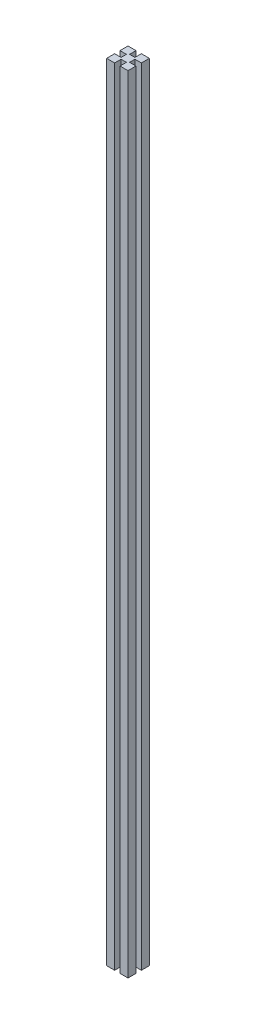
SolidWorks part; units mm, degrees
ref_plane "Front Plane" through (0, 0, 0) normal (0, 0, 1) x (1, 0, 0)
ref_plane "Top Plane" through (0, 0, 0) normal (0, 1, 0) x (1, 0, 0)
ref_plane "Right Plane" through (0, 0, 0) normal (1, 0, 0) x (0, 0, -1)
sketch "Sketch1" plane through (0, 0, 0) normal (0, 1, 0) x (1, 0, 0)
  line L1 (-10, -10) -> (10, -10)
  line L2 (-10, -10) -> (-10, 10)
  line L3 (-10, 10) -> (10, 10)
  line L4 (10, -10) -> (10, 10)
  line L5 (-10, -10) -> (10, 10) construction
  line L6 (-10, 10) -> (10, -10) construction
  point P0 (0, 0)
  dimension "D1" = 20
  dimension "D2" = 20
extrude "Boss-Extrude1" add sketch "Sketch1" along normal blind 368.3 and the other way blind 368.3
sketch "Sketch2" plane through (0, 0, 0) normal (0, 1, 0) x (1, 0, 0)
  line L0 (-2.5, 4) -> (2.5, 4)
  line L1 (-2.5, 4) -> (-2.5, 16)
  line L2 (-2.5, 16) -> (2.5, 16)
  line L3 (2.5, 4) -> (2.5, 16)
  line L4 (-2.5, 4) -> (2.5, 16) construction
  line L5 (-2.5, 16) -> (2.5, 4) construction
  line L6 (4, 2.5) -> (16, 2.5)
  line L7 (4, 2.5) -> (4, -2.5)
  line L8 (4, -2.5) -> (16, -2.5)
  line L9 (16, 2.5) -> (16, -2.5)
  line L10 (4, 2.5) -> (16, -2.5) construction
  line L11 (4, -2.5) -> (16, 2.5) construction
  line L12 (-10, 10) -> (10, -10) construction
  line L13 (-16, 2.5) -> (-4, -2.5) construction
  line L14 (-4, 2.5) -> (-16, -2.5) construction
  line L15 (-4, -2.5) -> (-16, -2.5)
  line L16 (-16, 2.5) -> (-16, -2.5)
  line L17 (-4, 2.5) -> (-16, 2.5)
  line L18 (-4, 2.5) -> (-4, -2.5)
  line L19 (2.5, -4) -> (2.5, -16)
  line L20 (2.5, -4) -> (-2.5, -16) construction
  line L21 (-2.5, -4) -> (2.5, -16) construction
  line L22 (-2.5, -16) -> (2.5, -16)
  line L23 (-2.5, -4) -> (2.5, -4)
  line L24 (-2.5, -4) -> (-2.5, -16)
  line L25 (-10, 10) -> (-10, -10) construction
  line L26 (10, -10) -> (10, 10) construction
  line L27 (-10, -10) -> (10, -10) construction
  line L28 (10, 10) -> (-10, 10) construction
  point P0 (0, 10)
  point P5 (10, 0)
  point P16 (-10, 0)
  point P21 (0, -10)
  dimension "D1" = 5
  dimension "D2" = 12
  dimension "D3" = 5
  dimension "D4" = 12
extrude "Cut-Extrude1" cut sketch "Sketch2" against normal through all both and the other way through all
